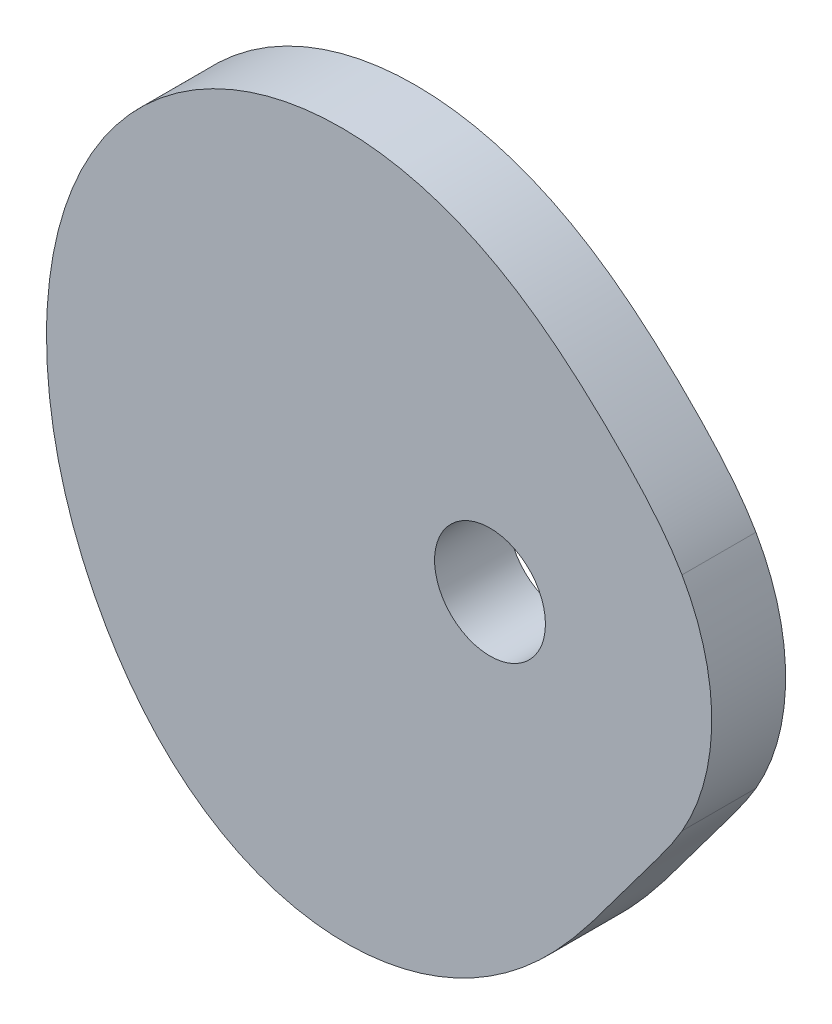
SolidWorks part; units mm, degrees
material "Plain Carbon Steel"
ref_plane "Front Plane" through (0, 0, 0) normal (0, 0, 1) x (1, 0, 0)
ref_plane "Top Plane" through (0, 0, 0) normal (0, 1, 0) x (1, 0, 0)
ref_plane "Right Plane" through (0, 0, 0) normal (1, 0, 0) x (0, 0, -1)
sketch "Displacement Sketch" plane through (0, 0, 0) normal (0, 0, 1) x (1, 0, 0)
  line L0 (0, 30) -> (0, 0) construction
  line L1 (0, 0) -> (94.2478, 0) construction
  line L2 (7.854, 0) -> (7.854, 30) construction
  line L3 (47.1239, 0) -> (47.1239, 30) construction
  line L4 (54.9779, 0) -> (54.9779, 30) construction
  line L5 (86.3938, 0) -> (86.3938, 30) construction
  line L6 (94.2478, 0) -> (94.2478, 30) construction
  line L7 (0, 0) -> (7.854, 0)
  line L8 (54.9779, 30) -> (47.1239, 30)
  line L9 (86.3938, 0) -> (94.2478, 0)
  spline S0 degree 4 poles (3.9269, -0.1935) (4.0488, -0.1758) (4.2317, -0.1512) (4.4758, -0.1225) (4.8422, -0.0867) (5.2163, -0.0578) (5.6253, -0.033) (6.1641, -0.0149) (6.6727, -0.0023) (7.5608, 0.0009) (8.0245, -0.0008) (8.9912, 0.0018) (9.6326, 0.0153) (10.4336, 0.0487) (11.2193, 0.114) (12.1687, 0.239) (13.2272, 0.4631) (14.3617, 0.8184) (15.4442, 1.2981) (16.3961, 1.8311) (17.2356, 2.3899) (17.9769, 2.9506) (18.9867, 3.8052) (20.4569, 5.2481) (22.2561, 7.369) (24.316, 10.1965) (26.445, 13.3901) (28.5329, 16.6099) (30.662, 19.8035) (32.7216, 22.631) (34.6767, 24.9351) (36.4888, 26.6721) (37.9762, 27.8085) (39.3257, 28.611) (40.6201, 29.1815) (41.744, 29.5369) (42.8204, 29.761) (43.9149, 29.9098) (44.9503, 29.9752) (45.7975, 29.9975) (46.9452, 30.0008) (47.4226, 29.9991) (48.301, 30.0023) (48.8161, 30.0149) (49.351, 30.033) (49.8217, 30.0613) (50.3222, 30.1019) (50.6845, 30.1431) (50.9289, 30.1758) (51.0512, 30.1935) knots 0 0 0 0 0 0.008159 0.012239 0.016318 0.024478 0.032637 0.040796 0.048955 0.065274 0.077237 0.0892 0.101163 0.113126 0.127947 0.142767 0.163984 0.185201 0.206418 0.221307 0.236195 0.252108 0.268021 0.309045 0.372696 0.436348 0.5 0.563652 0.627304 0.690955 0.731979 0.763805 0.793582 0.814799 0.836016 0.857233 0.872053 0.886874 0.9108 0.922763 0.934726 0.951045 0.959204 0.967363 0.975522 0.983682 0.991841 1 1 1 1 1 construction
  spline S1 degree 4 poles (7.854, 0) (8.0108, 0) (8.3267, 0) (8.9912, 0.0018) (9.6326, 0.0153) (10.4336, 0.0487) (11.2193, 0.114) (12.1687, 0.239) (13.2272, 0.4631) (14.3617, 0.8184) (15.4442, 1.2981) (16.3961, 1.8311) (17.2356, 2.3899) (17.9769, 2.9506) (18.9867, 3.8052) (20.4569, 5.2481) (22.2561, 7.369) (24.316, 10.1965) (26.445, 13.3901) (28.5329, 16.6099) (30.662, 19.8035) (32.7216, 22.631) (34.6767, 24.9351) (36.4888, 26.6721) (37.9762, 27.8085) (39.3257, 28.611) (40.6201, 29.1815) (41.744, 29.5369) (42.8204, 29.761) (43.9149, 29.9098) (44.9503, 29.9752) (45.7975, 29.9975) (46.6533, 30) (46.9671, 30) (47.1239, 30) knots 0.065274 0.065274 0.065274 0.065274 0.065274 0.077237 0.0892 0.101163 0.113126 0.127947 0.142767 0.163984 0.185201 0.206418 0.221307 0.236195 0.252108 0.268021 0.309045 0.372696 0.436348 0.5 0.563652 0.627304 0.690955 0.731979 0.763805 0.793582 0.814799 0.836016 0.857233 0.872053 0.886874 0.9108 0.922763 0.934726 0.934726 0.934726 0.934726 0.934726
  spline S2 degree 4 poles (51.8364, 30.1935) (51.9333, 30.1759) (52.0776, 30.1514) (52.277, 30.1227) (52.5134, 30.0929) (52.7252, 30.0724) (52.9382, 30.0508) (53.3985, 30.0242) (53.803, 30.0039) (54.6558, 29.9989) (55.1209, 30.0008) (55.8637, 29.9983) (56.3785, 29.9855) (56.984, 29.9549) (57.563, 29.898) (58.1546, 29.8088) (58.7211, 29.6832) (59.2659, 29.5246) (59.7759, 29.3366) (60.3987, 29.0588) (61.0345, 28.7042) (61.6761, 28.269) (62.3324, 27.7409) (62.9038, 27.2183) (63.779, 26.3231) (64.9795, 24.8654) (66.3897, 22.7998) (67.9674, 20.1176) (69.518, 17.2414) (71.0266, 14.3433) (72.5472, 11.4515) (74.1369, 8.5963) (75.687, 6.1171) (77.071, 4.2628) (78.2206, 3.0117) (79.0935, 2.2059) (79.8697, 1.5938) (80.6725, 1.0885) (81.4863, 0.699) (82.2071, 0.4402) (82.8361, 0.2678) (83.4919, 0.1447) (84.1237, 0.0652) (84.8081, 0.0212) (85.3823, 0.0025) (86.2047, -0.001) (86.6994, 0.0013) (87.5567, -0.0039) (88.024, -0.026) (88.5339, -0.0579) (88.7912, -0.0869) (89.0549, -0.1167) (89.2409, -0.1442) (89.3905, -0.1677) (89.4872, -0.1847) (89.5353, -0.1935) knots 0 0 0 0 0 0.007472 0.011208 0.014944 0.01868 0.022416 0.029888 0.044832 0.059777 0.070524 0.081272 0.09202 0.102768 0.114604 0.126441 0.136767 0.147094 0.15742 0.167746 0.188398 0.202259 0.21612 0.231609 0.247099 0.297177 0.359134 0.421092 0.48305 0.545008 0.606966 0.668924 0.730882 0.766656 0.782145 0.797635 0.820922 0.841574 0.853821 0.866069 0.878735 0.891402 0.903607 0.915813 0.928018 0.940223 0.955168 0.970112 0.977584 0.985056 0.988792 0.992528 0.996264 1 1 1 1 1 construction
  spline S3 degree 4 poles (54.9779, 30) (55.1026, 30) (55.3562, 30) (55.8637, 29.9983) (56.3785, 29.9855) (56.984, 29.9549) (57.563, 29.898) (58.1546, 29.8088) (58.7211, 29.6832) (59.2659, 29.5246) (59.7759, 29.3366) (60.3987, 29.0588) (61.0345, 28.7042) (61.6761, 28.269) (62.3324, 27.7409) (62.9038, 27.2183) (63.779, 26.3231) (64.9795, 24.8654) (66.3897, 22.7998) (67.9674, 20.1176) (69.518, 17.2414) (71.0266, 14.3433) (72.5472, 11.4515) (74.1369, 8.5963) (75.687, 6.1171) (77.071, 4.2628) (78.2206, 3.0117) (79.0935, 2.2059) (79.8697, 1.5938) (80.6725, 1.0885) (81.4863, 0.699) (82.2071, 0.4402) (82.8361, 0.2678) (83.4919, 0.1447) (84.1237, 0.0652) (84.8081, 0.0212) (85.3823, 0.0025) (85.9663, 0) (86.2521, 0) (86.3938, 0) knots 0.059777 0.059777 0.059777 0.059777 0.059777 0.070524 0.081272 0.09202 0.102768 0.114604 0.126441 0.136767 0.147094 0.15742 0.167746 0.188398 0.202259 0.21612 0.231609 0.247099 0.297177 0.359134 0.421092 0.48305 0.545008 0.606966 0.668924 0.730882 0.766656 0.782145 0.797635 0.820922 0.841574 0.853821 0.866069 0.878735 0.891402 0.903607 0.915813 0.928018 0.940223 0.940223 0.940223 0.940223 0.940223
  dimension "D1" = 30
  dimension "D2" = 94.2478
  dimension "D3" = 7.854
  dimension "D4" = 39.2699
  dimension "D5" = 7.854
  dimension "D6" = 31.4159
  dimension "D7" = 7.854
sketch "Cam Profile Sketch" plane through (0, 0, 0) normal (0, 0, 1) x (1, 0, 0)
  line L0 (-50, 0) -> (-110, 0) construction
  line L1 (-50, 0) -> (-24.0192, 15) construction
  line L3 (-50, 0) -> (-101.9615, -30) construction
  line L4 (-24.0192, -15) -> (-50, 0) construction
  circle A1 centre (-50, 0) radius 30 construction
  arc A2 (-110, 0) -> (-101.9615, -30) centre (-50, 0) ccw
  arc A3 (-24.0192, -15) -> (-24.0192, 15) centre (-50, 0) ccw
  spline S0 degree 4 poles (-21.2091, 7.7145) (-21.2858, 8.1159) (-21.4614, 8.9142) (-21.7573, 9.9785) (-22.172, 11.1543) (-22.5425, 12.0629) (-22.8328, 12.7157) (-23.0475, 13.1702) (-23.2367, 13.553) (-23.3977, 13.8678) (-23.5315, 14.1223) (-23.6743, 14.3864) (-23.8234, 14.6558) (-23.963, 14.9031) (-24.078, 15.1023) (-24.2251, 15.3513) (-24.3879, 15.6222) (-24.5484, 15.8834) (-24.7046, 16.132) (-24.9002, 16.4369) (-25.141, 16.8032) (-25.4296, 17.2296) (-25.8496, 17.8292) (-26.3646, 18.5342) (-26.9803, 19.3379) (-27.7029, 20.2357) (-28.4399, 21.1127) (-29.193, 21.9759) (-29.9599, 22.8268) (-30.7389, 23.6667) (-31.5284, 24.4968) (-32.5067, 25.5024) (-33.6805, 26.6768) (-35.0572, 28.0122) (-36.647, 29.4971) (-38.2677, 30.9482) (-39.9231, 32.3599) (-42.0405, 34.0664) (-44.6652, 36.007) (-47.861, 38.0826) (-51.7272, 40.1574) (-55.7694, 41.8669) (-59.9611, 43.1699) (-64.2655, 44.0331) (-68.6061, 44.4325) (-72.9648, 44.3571) (-77.2885, 43.798) (-81.5219, 42.7551) (-85.6093, 41.2376) (-89.5077, 39.2582) (-93.1648, 36.8399) (-96.1106, 34.3683) (-98.4314, 32.0176) (-100.2147, 29.9232) (-101.5479, 28.1724) (-102.7851, 26.3526) (-104.2222, 23.9781) (-105.5019, 21.4855) (-106.4991, 19.1642) (-107.2657, 17.0493) (-107.7851, 15.4574) (-108.1706, 14.1375) (-108.5154, 12.8065) (-108.8203, 11.4659) (-109.0404, 10.3882) (-109.237, 9.3062) (-109.4104, 8.2199) (-109.5609, 7.1306) (-109.6888, 6.0379) (-109.7944, 4.9438) (-109.8782, 3.8459) (-109.9326, 2.8875) (-109.966, 2.0581) (-109.9852, 1.3821) (-109.9954, 0.8266) (-110, 0.2418) (-110.0005, -0.1085) (-109.9977, -0.5463) (-109.9928, -0.9634) (-109.9836, -1.4543) (-109.9677, -2.021) (-109.9422, -2.7002) (-109.9037, -3.4694) (-109.8439, -4.4322) (-109.7539, -5.5857) (-109.6229, -6.9296) (-109.4387, -8.4614) (-109.2212, -9.989) (-109.0339, -11.131) (-108.8987, -11.8905) (-108.8286, -12.2697) knots 0 0 0 0 0 0.011381 0.022762 0.030729 0.034712 0.038695 0.042679 0.04467 0.046662 0.048654 0.050645 0.052637 0.054629 0.05667 0.058711 0.060752 0.062793 0.064834 0.066875 0.070958 0.07504 0.079122 0.087287 0.095263 0.103239 0.111216 0.119192 0.127168 0.135144 0.143121 0.151097 0.166243 0.18139 0.196536 0.211683 0.226829 0.241976 0.272269 0.302562 0.332855 0.364025 0.394318 0.424611 0.454904 0.485197 0.51549 0.545783 0.576076 0.60637 0.637 0.667631 0.682947 0.698262 0.713578 0.728893 0.744209 0.775529 0.791533 0.799191 0.806849 0.822164 0.829822 0.83748 0.845138 0.852795 0.860453 0.868111 0.875768 0.883426 0.891084 0.898742 0.902571 0.906399 0.910228 0.914057 0.916743 0.919429 0.922114 0.9248 0.930171 0.935543 0.940914 0.946286 0.957029 0.967771 0.978514 0.989257 1 1 1 1 1 construction
  spline S1 degree 4 poles (-24.0192, 15) (-24.0507, 15.0545) (-24.1141, 15.1634) (-24.2251, 15.3513) (-24.3879, 15.6222) (-24.5484, 15.8834) (-24.7046, 16.132) (-24.9002, 16.4369) (-25.141, 16.8032) (-25.4296, 17.2296) (-25.8496, 17.8292) (-26.3646, 18.5342) (-26.9803, 19.3379) (-27.7029, 20.2357) (-28.4399, 21.1127) (-29.193, 21.9759) (-29.9599, 22.8268) (-30.7389, 23.6667) (-31.5284, 24.4968) (-32.5067, 25.5024) (-33.6805, 26.6768) (-35.0572, 28.0122) (-36.647, 29.4971) (-38.2677, 30.9482) (-39.9231, 32.3599) (-42.0405, 34.0664) (-44.6652, 36.007) (-47.861, 38.0826) (-51.7272, 40.1574) (-55.7694, 41.8669) (-59.9611, 43.1699) (-64.2655, 44.0331) (-68.6061, 44.4325) (-72.9648, 44.3571) (-77.2885, 43.798) (-81.5219, 42.7551) (-85.6093, 41.2376) (-89.5077, 39.2582) (-93.1648, 36.8399) (-96.1106, 34.3683) (-98.4314, 32.0176) (-100.2147, 29.9232) (-101.5479, 28.1724) (-102.7851, 26.3526) (-104.2222, 23.9781) (-105.5019, 21.4855) (-106.4991, 19.1642) (-107.2657, 17.0493) (-107.7851, 15.4574) (-108.1706, 14.1375) (-108.5154, 12.8065) (-108.8203, 11.4659) (-109.0404, 10.3882) (-109.237, 9.3062) (-109.4104, 8.2199) (-109.5609, 7.1306) (-109.6888, 6.0379) (-109.7944, 4.9438) (-109.8782, 3.8459) (-109.9326, 2.8875) (-109.966, 2.0581) (-109.9852, 1.3821) (-109.9954, 0.8266) (-109.9992, 0.3526) (-110, 0.1181) (-110, 0) knots 0.054629 0.054629 0.054629 0.054629 0.054629 0.05667 0.058711 0.060752 0.062793 0.064834 0.066875 0.070958 0.07504 0.079122 0.087287 0.095263 0.103239 0.111216 0.119192 0.127168 0.135144 0.143121 0.151097 0.166243 0.18139 0.196536 0.211683 0.226829 0.241976 0.272269 0.302562 0.332855 0.364025 0.394318 0.424611 0.454904 0.485197 0.51549 0.545783 0.576076 0.60637 0.637 0.667631 0.682947 0.698262 0.713578 0.728893 0.744209 0.775529 0.791533 0.799191 0.806849 0.822164 0.829822 0.83748 0.845138 0.852795 0.860453 0.868111 0.875768 0.883426 0.891084 0.898742 0.902571 0.906399 0.910228 0.914057 0.914057 0.914057 0.914057 0.914057
  spline S2 degree 4 poles (-21.6523, -9.2107) (-21.6911, -9.3816) (-21.7734, -9.7223) (-21.9112, -10.2297) (-22.1221, -10.8983) (-22.3358, -11.4956) (-22.5438, -12.0239) (-22.739, -12.4851) (-22.9165, -12.8818) (-23.1022, -13.2758) (-23.2929, -13.6626) (-23.4891, -14.0434) (-23.7057, -14.4452) (-23.9205, -14.8291) (-24.0616, -15.0746) (-24.2663, -15.4211) (-24.5217, -15.8436) (-24.7937, -16.2763) (-25.1179, -16.7754) (-25.451, -17.2732) (-25.7889, -17.7647) (-26.1324, -18.253) (-26.5254, -18.801) (-26.9688, -19.4078) (-27.463, -20.0731) (-28.0074, -20.7972) (-28.6909, -21.7003) (-29.5123, -22.783) (-30.4671, -24.0488) (-31.5493, -25.5022) (-32.6238, -26.9613) (-33.6957, -28.4223) (-35.0415, -30.2443) (-36.6815, -32.4119) (-38.665, -34.8872) (-41.0725, -37.5988) (-43.7531, -40.2586) (-46.631, -42.7058) (-49.7079, -44.8991) (-52.9736, -46.7997) (-56.2658, -48.3277) (-59.691, -49.5298) (-63.2203, -50.3807) (-66.8194, -50.8597) (-70.4494, -50.9522) (-74.0906, -50.649) (-77.6987, -49.9429) (-80.7843, -48.9751) (-83.3578, -47.9009) (-85.4314, -46.8553) (-87.4469, -45.7017) (-89.3793, -44.4112) (-91.2213, -42.9953) (-92.9688, -41.4661) (-94.173, -40.3103) (-95.2008, -39.245) (-96.0682, -38.2877) (-96.7885, -37.452) (-97.4606, -36.6328) (-98.0873, -35.8334) (-98.6714, -35.0558) (-99.2148, -34.3037) (-99.7454, -33.5401) (-100.2603, -32.7705) (-100.7025, -32.0835) (-101.069, -31.4972) (-101.3683, -31.0064) (-101.6217, -30.5819) (-101.8961, -30.1147) (-102.0953, -29.7685) (-102.4399, -29.1592) (-102.7353, -28.6215) (-103.033, -28.0673) (-103.3278, -27.5059) (-103.688, -26.8034) (-104.1102, -25.9547) (-104.588, -24.9573) (-105.1148, -23.8084) (-105.6233, -22.6513) (-105.9916, -21.7779) (-106.2316, -21.1933) (-106.3502, -20.9004) knots 0 0 0 0 0 0.005965 0.01193 0.017895 0.023861 0.027557 0.031254 0.034951 0.038647 0.042344 0.046041 0.049738 0.053434 0.055975 0.058515 0.063596 0.068678 0.073759 0.07884 0.083921 0.089002 0.094083 0.101794 0.109505 0.117216 0.124927 0.140349 0.155772 0.171194 0.186616 0.202038 0.21746 0.248304 0.279149 0.309993 0.340837 0.376763 0.407607 0.438451 0.469296 0.50014 0.530984 0.561829 0.592673 0.623517 0.655127 0.686736 0.702541 0.718346 0.73415 0.76576 0.781565 0.797369 0.813174 0.822563 0.831952 0.841341 0.85073 0.858632 0.866534 0.874437 0.882339 0.890242 0.898144 0.902095 0.906046 0.909997 0.913949 0.919327 0.924705 0.930083 0.935461 0.94084 0.946218 0.956974 0.967731 0.978487 0.989244 1 1 1 1 1 construction
  spline S3 degree 4 poles (-24.0192, -15) (-24.0513, -15.0556) (-24.1162, -15.167) (-24.2663, -15.4211) (-24.5217, -15.8436) (-24.7937, -16.2763) (-25.1179, -16.7754) (-25.451, -17.2732) (-25.7889, -17.7647) (-26.1324, -18.253) (-26.5254, -18.801) (-26.9688, -19.4078) (-27.463, -20.0731) (-28.0074, -20.7972) (-28.6909, -21.7003) (-29.5123, -22.783) (-30.4671, -24.0488) (-31.5493, -25.5022) (-32.6238, -26.9613) (-33.6957, -28.4223) (-35.0415, -30.2443) (-36.6815, -32.4119) (-38.665, -34.8872) (-41.0725, -37.5988) (-43.7531, -40.2586) (-46.631, -42.7058) (-49.7079, -44.8991) (-52.9736, -46.7997) (-56.2658, -48.3277) (-59.691, -49.5298) (-63.2203, -50.3807) (-66.8194, -50.8597) (-70.4494, -50.9522) (-74.0906, -50.649) (-77.6987, -49.9429) (-80.7843, -48.9751) (-83.3578, -47.9009) (-85.4314, -46.8553) (-87.4469, -45.7017) (-89.3793, -44.4112) (-91.2213, -42.9953) (-92.9688, -41.4661) (-94.173, -40.3103) (-95.2008, -39.245) (-96.0682, -38.2877) (-96.7885, -37.452) (-97.4606, -36.6328) (-98.0873, -35.8334) (-98.6714, -35.0558) (-99.2148, -34.3037) (-99.7454, -33.5401) (-100.2603, -32.7705) (-100.7025, -32.0835) (-101.069, -31.4972) (-101.3683, -31.0064) (-101.6217, -30.5819) (-101.8104, -30.2605) (-101.9116, -30.0865) (-101.9615, -30) knots 0.053434 0.053434 0.053434 0.053434 0.053434 0.055975 0.058515 0.063596 0.068678 0.073759 0.07884 0.083921 0.089002 0.094083 0.101794 0.109505 0.117216 0.124927 0.140349 0.155772 0.171194 0.186616 0.202038 0.21746 0.248304 0.279149 0.309993 0.340837 0.376763 0.407607 0.438451 0.469296 0.50014 0.530984 0.561829 0.592673 0.623517 0.655127 0.686736 0.702541 0.718346 0.73415 0.76576 0.781565 0.797369 0.813174 0.822563 0.831952 0.841341 0.85073 0.858632 0.866534 0.874437 0.882339 0.890242 0.898144 0.902095 0.906046 0.909997 0.913949 0.913949 0.913949 0.913949 0.913949
  point P4 (0, 0)
  dimension "D2" = 30
  dimension "D1" = 50
  dimension "D3" = 60
  dimension "D4" = 30
  dimension "D6" = 30
  dimension "D7" = 30
  dimension "D8" = 180
extrude "Boss-Extrude1" add sketch "Cam Profile Sketch" along normal mid plane 10 contours S1 A2 S3 A3
sketch "Sketch2" plane through (0, 0, 0) normal (0, 0, 1) x (1, 0, 0)
  circle A0 centre (-50, 0) radius 7.5
  dimension "D1" = 15
extrude "Cut-Extrude2" cut sketch "Sketch2" against normal up to next and the other way up to next
equation "\"Dwell Angle 1\"= 30"
equation "\"Rise Angle\"= 150"
equation "\"Dwell Angle 2\"= 30"
equation "\"Return Angle\"= 120"
equation "\"Dwell Angle 3\"= 30"
equation "\"Prime Circle Radius\" = 40"
equation "\"Roller Radius\"= 10"
equation "\"Base Circle Radius\"= \"Prime Circle Radius\" - \"Roller Radius\""
equation "\"Lift\" = 30"
equation "\"D1@Displacement Sketch\" = \"Lift\""
equation "\"D2@Displacement Sketch\" = \"Lift\" * pi"
equation "\"Dwell Radians 1\"= \"Dwell Angle 1\" * pi / 180"
equation "\"Rise Radians\"= \"Rise Angle\" * pi / 180"
equation "\"Dwell Radians 2\"= \"Dwell Angle 2\" * pi / 180"
equation "\"Return Radians\"= \"Return Angle\" * pi / 180"
equation "\"Dwell Radian 3\"= \"Dwell Angle 3\" * pi / 180"
equation "\"D3@Displacement Sketch\"=\"Dwell Radians 1\" * \"Lift\" / 2"
equation "\"D4@Displacement Sketch\"=\"Rise Radians\" * \"Lift\" / 2"
equation "\"D5@Displacement Sketch\"=\"Dwell Radians 2\" * \"Lift\" / 2"
equation "\"D6@Displacement Sketch\"=\"Return Radians\" * \"Lift\" / 2"
equation "\"D7@Displacement Sketch\"=\"Dwell Radian 3\" * \"Lift\" / 2"
equation "\"D2@Cam Profile Sketch\" = \"Base Circle Radius\""
equation "\"D3@Cam Profile Sketch\" = \"Base Circle Radius\" + \"Lift\""
equation "\"D8@Cam Profile Sketch\" = \"Dwell Angle 1\" + \"Rise Angle\""
equation "\"D6@Cam Profile Sketch\" = \"Dwell Angle 2\""
equation "\"D1@Cam Profile Sketch\" = \"Base Circle Radius\" + 20"
